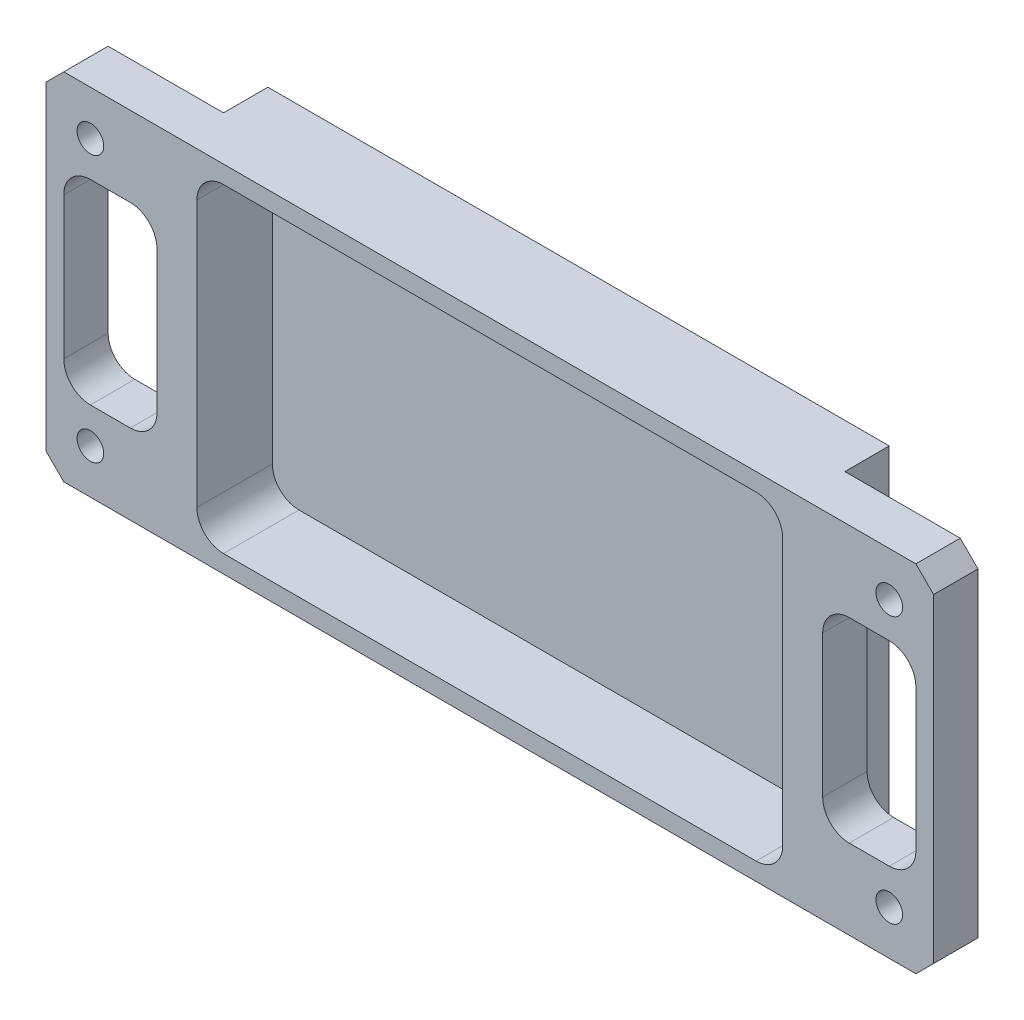
SolidWorks part; units mm, degrees
material "ABS"
ref_plane "Ebene vorne" through (0, 0, 0) normal (0, 0, 1) x (1, 0, 0)
ref_plane "Ebene oben" through (0, 0, 0) normal (0, 1, 0) x (1, 0, 0)
ref_plane "Ebene rechts" through (0, 0, 0) normal (1, 0, 0) x (0, 0, -1)
sketch "Skizze1" plane through (0, 0, 0) normal (0, 0, 1) x (1, 0, 0)
  line L0 (0, 52.8107) -> (0, -52.2189) construction
  line L1 (-65.5195, 0) -> (67.0248, 0) construction
  line L2 (-50, -20) -> (-50, 20)
  line L3 (-50, 20) -> (50, 20)
  line L4 (50, -20) -> (50, 20)
  line L5 (-50, -20) -> (50, -20)
  point P9 (0, 20)
  point P10 (0, -20)
  point P12 (50, 0)
  point P13 (-50, 0)
  dimension "D1" = 40
  dimension "D2" = 100
extrude "Aufsatz-Linear austragen1" add sketch "Skizze1" along normal blind 2.5 and the other way blind 2.5
sketch "Skizze2" plane through (0, 0, 0) normal (0, 0, 1) x (1, 0, 0)
  line L0 (0, 30.9245) -> (0, -26.0823) construction
  line L1 (-65.8109, 0) -> (54.5857, 0) construction
  circle A0 centre (-45, 15) radius 1.5
  circle A1 centre (-45, -15) radius 1.5
  circle A2 centre (45, -15) radius 1.5
  circle A3 centre (45, 15) radius 1.5
  dimension "D3" = 3
  dimension "D1" = 30
  dimension "D2" = 90
extrude "Schnitt-Linear austragen1" cut sketch "Skizze2" against normal through all and the other way through all
sketch "Skizze4" plane through (0, 0, 0) normal (0, 0, 1) x (1, 0, 0)
  line L0 (0, 35.9786) -> (0, -30.5696) construction
  line L1 (-57.4553, 0) -> (60.3332, 0) construction
  line L2 (-48, -8) -> (-48, 8)
  line L3 (-45, 11) -> (-40.5, 11)
  line L4 (-37.5, 8) -> (-37.5, -8)
  line L5 (-45, -11) -> (-40.5, -11)
  line L6 (45, -11) -> (40.5, -11)
  line L7 (37.5, 8) -> (37.5, -8)
  line L8 (45, 11) -> (40.5, 11)
  line L9 (48, -8) -> (48, 8)
  arc A0 (-37.5, -8) -> (-40.5, -11) centre (-40.5, -8) cw
  arc A1 (-45, -11) -> (-48, -8) centre (-45, -8) cw
  arc A2 (-37.5, 8) -> (-40.5, 11) centre (-40.5, 8) ccw
  arc A3 (-48, 8) -> (-45, 11) centre (-45, 8) cw
  arc A4 (48, 8) -> (45, 11) centre (45, 8) ccw
  arc A5 (37.5, 8) -> (40.5, 11) centre (40.5, 8) cw
  arc A6 (45, -11) -> (48, -8) centre (45, -8) ccw
  arc A7 (37.5, -8) -> (40.5, -11) centre (40.5, -8) ccw
  point P10 (-37.5, 0)
  point P11 (-48, 0)
  point P13 (-37.5, -11)
  point P16 (-48, -11)
  point P19 (-37.5, 11)
  point P22 (-48, 11)
  point P35 (48, 0)
  point P36 (37.5, 0)
  dimension "D4" = 3
  dimension "D1" = 22
  dimension "D2" = 48
  dimension "D3" = 37.5
extrude "Schnitt-Linear austragen2" cut sketch "Skizze4" against normal through all and the other way through all
sketch "Skizze7" plane through (0, 0, -2.5) normal (0, 0, -1) x (-1, 0, 0)
  line L0 (0, 37.0279) -> (0, -33.8129) construction
  line L1 (-65.6302, 0) -> (60.974, 0) construction
  line L2 (-35, 20) -> (-35, -20)
  line L3 (-50, 20) -> (50, 20) construction
  line L4 (-35, 20) -> (35, 20)
  line L6 (35, 20) -> (35, -20)
  line L7 (-35, -20) -> (35, -20)
  line L8 (-33, 18) -> (-33, -18) construction
  line L9 (-33, -18) -> (33, -18) construction
  line L10 (33, 18) -> (33, -18) construction
  line L11 (-33, 18) -> (33, 18) construction
  point P13 (0, 20)
  point P14 (0, -20)
  point P16 (35, 0)
  point P17 (-35, 0)
  dimension "D2" = 70
  dimension "D1" = 2
extrude "Aufsatz-Linear austragen3" add sketch "Skizze7" along normal blind 5
sketch "Skizze8" plane through (0, 0, 2.5) normal (0, 0, 1) x (1, 0, 0)
  line L0 (0, 38.5492) -> (0, -31.5223) construction
  line L1 (-74.5556, 0) -> (52.9258, 0) construction
  line L14 (33, -15) -> (33, 15)
  line L15 (-30, -18) -> (30, -18)
  line L16 (-33, 15) -> (-33, -15)
  line L17 (30, 18) -> (-30, 18)
  arc A0 (30, 18) -> (33, 15) centre (30, 15) cw
  arc A1 (-30, -18) -> (-33, -15) centre (-30, -15) cw
  arc A2 (30, -18) -> (33, -15) centre (30, -15) ccw
  arc A15 (-30, 18) -> (-33, 15) centre (-30, 15) ccw
  dimension "D3" = 3
  dimension "D1" = 36
  dimension "D2" = 66
extrude "Schnitt-Linear austragen6" cut sketch "Skizze8" against normal offset from surface (8.5 mm away) 1.5 up to face at (0, 0, -7.5)
chamfer "Fase1" distance 2 angle 45 4 edges at (-50, 20, 0) (-50, -20, 0) (50, 20, 0) (50, -20, 0)
